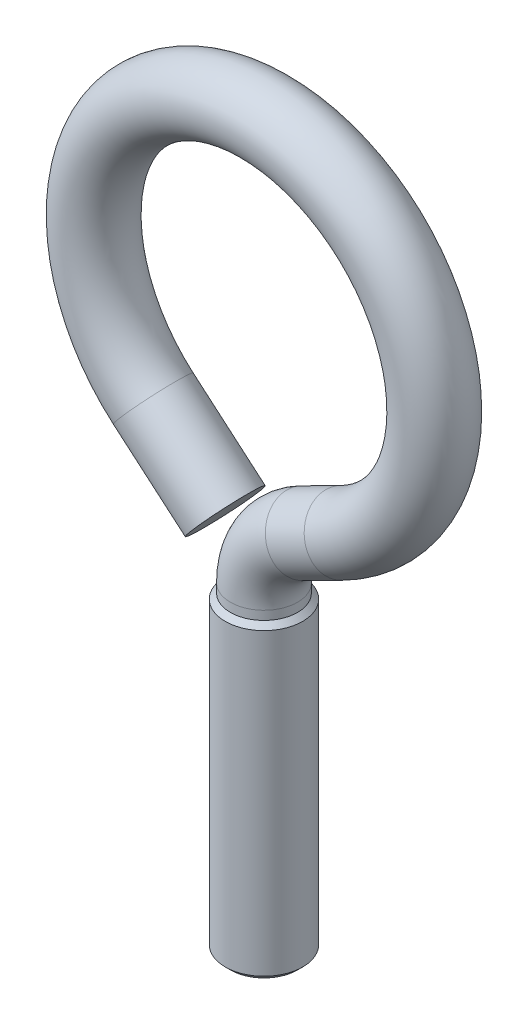
SolidWorks part; units mm, degrees
material "AISI 1015 钢，冷拔 (SS)"
ref_plane "前视基准面" through (0, 0, 0) normal (0, 0, 1) x (1, 0, 0)
ref_plane "上视基准面" through (0, 0, 0) normal (0, 1, 0) x (1, 0, 0)
ref_plane "右视基准面" through (0, 0, 0) normal (1, 0, 0) x (0, 0, -1)
sketch "Sketch29" plane through (0, 0, 0) normal (0, 1, 0) x (1, 0, 0)
  circle A0 centre (0, 0) radius 1.5
  dimension "螺纹大径" = 3
sketch "Sketch2" plane through (0, 0, 0) normal (0, 0, 1) x (1, 0, 0)
  line L0 (0, 0) -> (0, -12)
  dimension "螺杆长度" = 12
sweep "Sweep1" add profiles "Sketch29" path "Sketch2"
sketch "Sketch7" plane through (0, 0, 0) normal (0, 0, 1) x (1, 0, 0)
  line L0 (0, 0.3418) -> (0, 0)
  line L2 (2.9848, 3.5135) -> (1.4789, 2.7499)
  line L3 (-4.288, 4.3827) -> (-1.5, 2)
  line L7 (-1.5, 0) -> (-1.5, -12) construction
  arc A0 (2.9848, 3.5135) -> (-4.288, 4.3827) centre (0, 9.4) ccw
  arc A1 (0, 0.3418) -> (1.4789, 2.7499) centre (2.7, 0.3418) cw
  point P8 (0, 16)
  point P23 (0, 2)
  dimension "中径" = 6.6
  dimension "转弯半径" = 2.7
  dimension "圈高" = 14
  dimension "连接长度" = 2
sketch "Sketch28" plane through (0, 0, 0) normal (0, 1, 0) x (1, 0, 0)
  circle A0 centre (0, 0) radius 1.3
  dimension "线径" = 2.6
sweep "Sweep4" add profiles "Sketch28" path "Sketch7"
chamfer "Chamfer1" distance 0.2 angle 45 2 edges at (0, 0, 1.5) (0, -12, 1.5)
other "冻结***"
